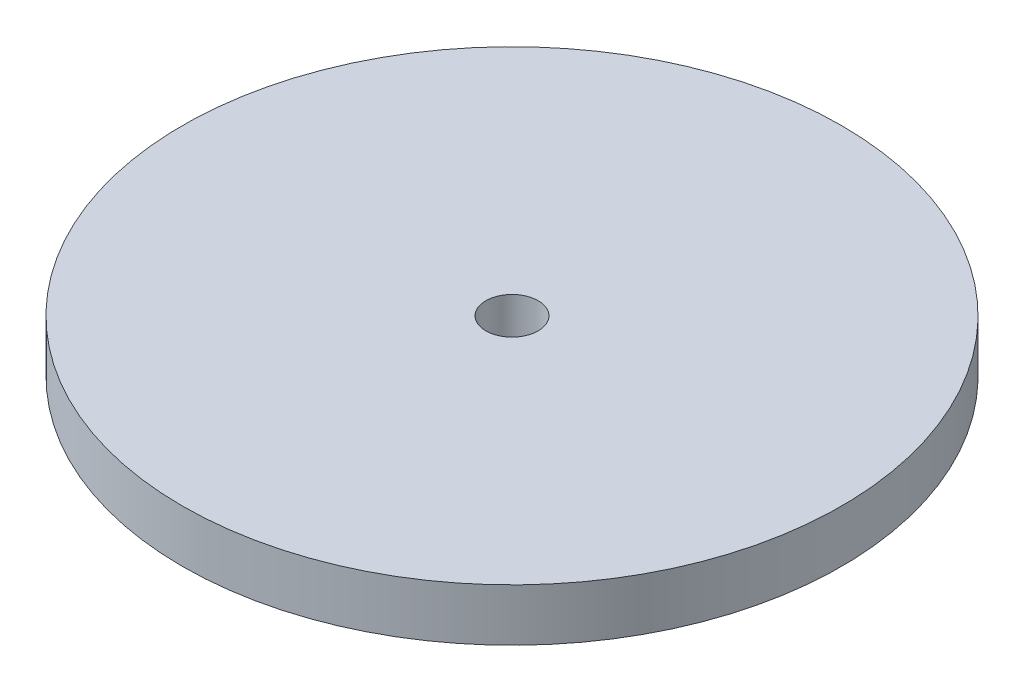
SolidWorks part; units mm, degrees
material "ABS"
ref_plane "Plan de face" through (0, 0, 0) normal (0, 0, 1) x (1, 0, 0)
ref_plane "Plan de dessus" through (0, 0, 0) normal (0, 1, 0) x (1, 0, 0)
ref_plane "Plan de droite" through (0, 0, 0) normal (1, 0, 0) x (0, 0, -1)
sketch "Esquisse1" plane through (0, 0, 0) normal (0, 1, 0) x (1, 0, 0)
  circle A0 centre (0, 0) radius 40
  dimension "D1" = 80
extrude "Boss.-Extru.1" add sketch "Esquisse1" along normal blind 6.35
sketch "Esquisse2" plane through (0, 0, 0) normal (0, -1, 0) x (1, 0, 0)
  circle A0 centre (0, 0) radius 3.175
  dimension "D1" = 6.35
extrude "Enlèv. mat.-Extru.1" cut sketch "Esquisse2" against normal up to surface (6.35 mm away) contours A0 up to face at (0, 6.35, 40)
